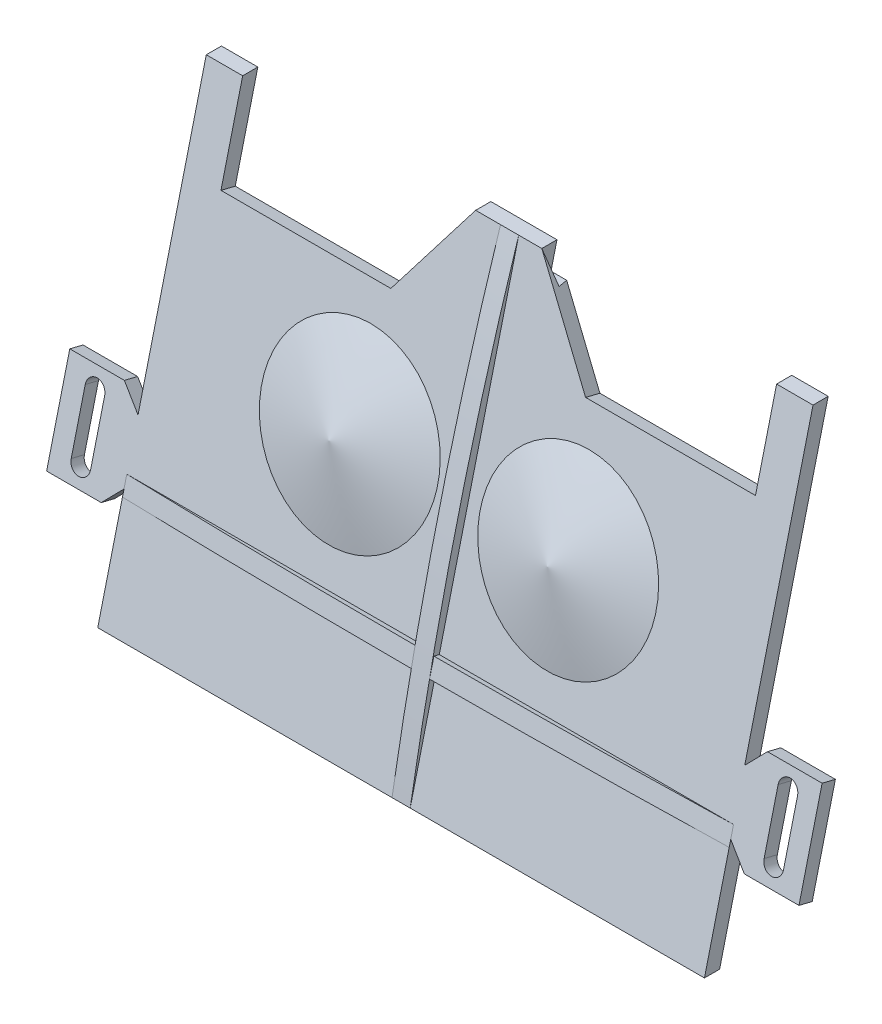
SolidWorks part; units mm, degrees
ref_plane "Alzado" through (0, 0, 0) normal (0, 0, 1) x (1, 0, 0)
ref_plane "Planta" through (0, 0, 0) normal (0, 1, 0) x (1, 0, 0)
ref_plane "Vista lateral" through (0, 0, 0) normal (1, 0, 0) x (0, 0, -1)
sketch "Croquis1" plane through (0, 0, 0) normal (1, 0, 0) x (0, 0, -1)
  line L0 (0, 0) -> (2.5, 0)
  line L1 (2.5, 0) -> (20.39, 72.8351)
  line L2 (0, 0) -> (17.89, 72.8351)
  line L3 (17.89, 72.8351) -> (20.39, 72.8351)
  line L4 (0, 0) -> (0, 2.8) construction
  line L5 (0, 2.8) -> (14.7473, 2.8) construction
  dimension "D1" = 2.5
  dimension "D2" = 75
  dimension "D3" = 13.8
  dimension "D4" = 2.8
extrude "Saliente-Extruir1" add sketch "Croquis1" against normal blind 100
sketch "Croquis7" plane through (0, 0, 0) normal (0, 0.2385, 0.9711) x (1, 0, 0)
  line L0 (-100, 75) -> (-100, 0) construction
  line L2 (-100, 0) -> (0, 0) construction
  circle A0 centre (-68, 40) radius 13.5
  circle A1 centre (-32.531, 40) radius 13.5
  dimension "D1" = 27
  dimension "D2" = 32
  dimension "D3" = 40
extrude "Cortar-Extruir3" cut sketch "Croquis7" against normal blind 10
sketch "Croquis11" plane through (0, 0, 0) normal (0, 0.2385, 0.9711) x (1, 0, 0)
  line L0 (-94, 81.9404) -> (-94, 60)
  line L2 (-94, 60) -> (-66, 60)
  line L5 (-34, 60.4083) -> (-6, 60.4083)
  line L6 (-6, 60.4083) -> (-6, 81.9404)
  line L7 (-100, 75) -> (-100, 0) construction
  line L8 (0, 75) -> (0, 0) construction
  line L10 (-66, 60) -> (-50.7863, 81.9404)
  line L11 (-50.7863, 81.9404) -> (-49.7863, 81.9404)
  line L12 (-49.7863, 81.9404) -> (-34, 60.4083)
  line L13 (-94, 81.9404) -> (-50.7863, 81.9404)
  line L14 (-49.7863, 81.9404) -> (-6, 81.9404)
  line L16 (-100, 0) -> (0, 0) construction
  line M10 (0, 75) -> (-100, 75)
  dimension "D1" = 28
  dimension "D2" = 6
  dimension "D3" = 6
  dimension "D4" = 1
  dimension "D5" = 60
extrude "Cortar-Extruir15" cut sketch "Croquis11" against normal blind 10 contours L2 L10 L0 M10 | L12 L5 L6 M10 region at (-77.2639, 65.9319, -16.1944) region at (-22.8175, 66.1286, -16.2427)
ref_plane "Plano1" through (-32, 0, 0) normal (1, 0, 0) x (0, 0, -1)
sketch "Croquis13" plane through (-32, 0, 0) normal (1, 0, 0) x (0, 0, -1)
  line L0 (0, 0) -> (17.89, 72.8351) construction
  line L1 (38.6494, 31.6957) -> (-31.0896, 48.8253) construction
  line L2 (31.7835, 18.4512) -> (-25.7464, 32.5819) construction
  line L3 (6.0826, 24.7639) -> (6.5597, 26.7062)
  line L4 (6.6279, 39.561) -> (6.0875, 39.6937)
  arc A0 (6.5597, 26.7062) -> (6.6279, 39.561) centre (188.146, 32.1694) cw
  arc A1 (6.0826, 24.7639) -> (6.0875, 39.6937) centre (188.146, 32.1694) cw
  dimension "D4" = 2
  dimension "D1" = 40
  dimension "D2" = 14.5
  dimension "D3" = 3
  dimension "D5" = 32.1694
revolve "Revolución1" add sketch "Croquis13" angle 360 about L1
ref_plane "mitad " through (-50, 0, 0) normal (1, 0, 0) x (0, 0, -1)
mirror "Simetría1" about plane through (-50, 0, 0) normal (1, 0, 0) of "Revolución1"
sketch "Croquis21" plane through (0, 72.8351, 0) normal (0, 1, 0) x (1, 0, 0)
  line L0 (-100, 20.39) -> (0, 20.39) construction
  line L1 (-94, 17.89) -> (-55.5988, 17.89)
  line L2 (-94, 17.89) -> (-94, 20.39)
  line L3 (-94, 20.39) -> (-55.5988, 20.39)
  line L4 (-55.5988, 17.89) -> (-55.5988, 20.39)
  line L5 (-55.5988, 17.89) -> (-94, 17.89) construction
  line L6 (-50.1484, 17.89) -> (-50.1484, 20.39) construction
  line L7 (-55.5988, 17.89) -> (-44.6979, 17.89) construction
  line L12 (-6, 17.89) -> (-44.6979, 17.89) construction
  line L13 (-44.6979, 17.89) -> (-6, 17.89)
  line L14 (-44.6979, 17.89) -> (-44.6979, 20.39)
  line L15 (-44.6979, 20.39) -> (-6, 20.39)
  line L16 (-6, 17.89) -> (-6, 20.39)
extrude "Cortar-Extruir19" cut sketch "Croquis21" against normal blind 4
ref_plane "Plano5" through (0, 0.5791, -0.1422) normal (0, 0.9711, -0.2385) x (1, 0, 0)
ref_plane "Plano6" through (0, 18.0595, -4.4358) normal (0, 0.9711, -0.2385) x (1, 0, 0)
sketch "Croquis33" plane through (0, 18.0595, -4.4358) normal (0, 0.9711, -0.2385) x (1, 0, 0)
  line L0 (0, 0) -> (-100, 0)
  arc A0 (0, 0) -> (-100, 0) centre (-50, 1371.4547) cw
  dimension "D1" = 1372.3658
extrude "Saliente-Extruir9" add sketch "Croquis33" along normal mid plane 3
sketch "Croquis35" plane through (-50, 0, 0) normal (1, 0, 0) x (0, 0, -1)
  line L0 (0, 0) -> (17.89, 72.8351)
  arc A0 (0, 0) -> (17.89, 72.8351) centre (520.5051, -89.2337) cw
  dimension "D1" = 528.0986
extrude "Saliente-Extruir10" add sketch "Croquis35" along normal mid plane 3
sketch "Croquis36" plane through (0, 0, 0) normal (0, 0.2385, 0.9711) x (1, 0, 0)
  line L1 (3, 31) -> (12, 31)
  line L2 (0, 27.8444) -> (0, 18.1556)
  line L3 (3, 15) -> (12, 15)
  line L4 (12, 31) -> (12, 15)
  line L5 (-50, 0) -> (-50, 8.5704) construction
  line L6 (-48.5, 0) -> (-51.5, 0) construction
  line L7 (0, 27.8444) -> (3, 31)
  line L8 (0, 18.1556) -> (3, 15)
  line L9 (7.1, 27.8444) -> (7.1, 18.1556) construction
  line L10 (8.7, 27.8444) -> (8.7, 18.1556)
  line L11 (5.5, 27.8444) -> (5.5, 18.1556)
  line L12 (-100, 18.1556) -> (-103, 15)
  line L13 (-100, 27.8444) -> (-100, 18.1556)
  line L14 (-100, 27.8444) -> (-103, 31)
  line L15 (-103, 31) -> (-112, 31)
  line L16 (-112, 31) -> (-112, 15)
  line L17 (-103, 15) -> (-112, 15)
  line L18 (-107.1, 27.8444) -> (-107.1, 18.1556) construction
  line L19 (-108.7, 27.8444) -> (-108.7, 18.1556)
  line L20 (-105.5, 27.8444) -> (-105.5, 18.1556)
  arc A0 (8.7, 27.8444) -> (5.5, 27.8444) centre (7.1, 27.8444) ccw
  arc A1 (5.5, 18.1556) -> (8.7, 18.1556) centre (7.1, 18.1556) ccw
  arc A2 (-108.7, 27.8444) -> (-105.5, 27.8444) centre (-107.1, 27.8444) cw
  arc A3 (-105.5, 18.1556) -> (-108.7, 18.1556) centre (-107.1, 18.1556) cw
  point P4 (7.1, 23)
  point P11 (0, 0)
  point P18 (0, 23)
  point P27 (-107.1, 23)
  point P32 (12, 23)
  dimension "D1" = 16
  dimension "D2" = 3.2
  dimension "D3" = 5.5
  dimension "D4" = 12
extrude "Saliente-Extruir11" add sketch "Croquis36" against normal blind 2.25
